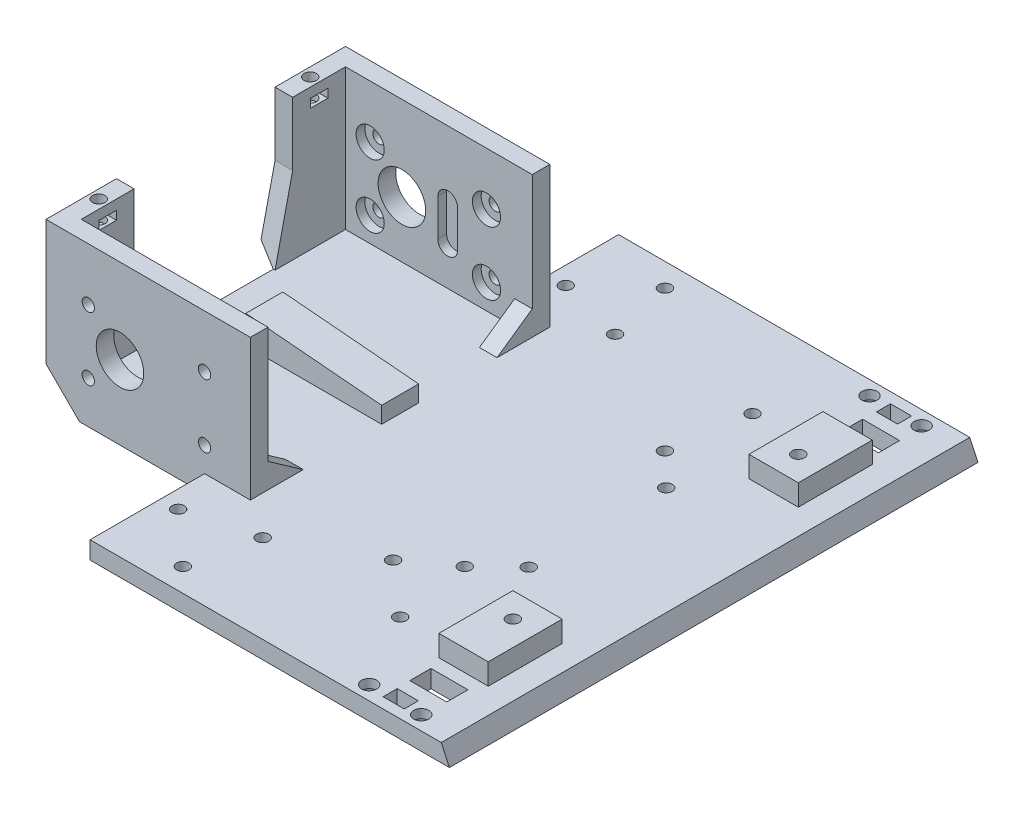
SolidWorks part; units mm, degrees
ref_plane "Front Plane" through (0, 0, 0) normal (0, 0, 1) x (1, 0, 0)
ref_plane "Top Plane" through (0, 0, 0) normal (0, 1, 0) x (1, 0, 0)
ref_plane "Right Plane" through (0, 0, 0) normal (1, 0, 0) x (0, 0, -1)
sketch "Sketch1" plane through (0, 0, 0) normal (0, 1, 0) x (1, 0, 0)
  line L0 (-25, 75) -> (-25, 42.5)
  line L1 (-25, -75) -> (77, -75)
  line L2 (-70, -42.5) -> (-70, 42.5)
  line L3 (-25, 75) -> (77, 75)
  line L4 (77, -75) -> (77, 75)
  line L7 (-25, 42.5) -> (-70, 42.5)
  line L8 (2, 0) -> (77, 0) construction
  line L9 (-25, -42.5) -> (-70, -42.5)
  line L10 (-25, -75) -> (-25, -42.5)
  point P0 (0, 0)
  dimension "D1" = 150
  dimension "D2" = 102
  dimension "D3" = 85
  dimension "D4" = 45
  dimension "D5" = 75
  dimension "D6" = 32.5
  dimension "D7" = 32.5
extrude "Boss-Extrude1" add sketch "Sketch1" along normal blind 5
sketch "Sketch3" plane through (0, 5, 0) normal (0, 1, 0) x (1, 0, 0)
  line L2 (-65, 17.5) -> (-70, 17.5)
  line L3 (-25, 42.5) -> (-70, 42.5) construction
  line L6 (-65, 17.5) -> (-65, 37.5)
  line L8 (0, 0) -> (-70, 0) construction
  line L9 (-70, 42.5) -> (-70, -42.5) construction
  line L17 (-65, 37.5) -> (-17, 37.5)
  line L18 (-12, 37.5) -> (-12, 42.5)
  line L19 (-12, 42.5) -> (-25, 42.5)
  line L20 (-25, 42.5) -> (-65, 42.5)
  line L28 (-12, 37.5) -> (-12, 27.5)
  line L29 (-12, 27.5) -> (-17, 27.5)
  line L30 (-17, 27.5) -> (-17, 37.5)
  line L40 (-70, -42.5) -> (-65, -42.5)
  line L41 (-70, 17.5) -> (-70, 42.5)
  line L42 (-70, 42.5) -> (-65, 42.5)
  line L43 (-70, -17.5) -> (-70, -42.5)
  line L44 (-17, -27.5) -> (-17, -37.5)
  line L45 (-12, -27.5) -> (-17, -27.5)
  line L46 (-12, -37.5) -> (-12, -27.5)
  line L47 (-25, -42.5) -> (-65, -42.5)
  line L48 (-12, -42.5) -> (-25, -42.5)
  line L49 (-12, -37.5) -> (-12, -42.5)
  line L50 (-65, -37.5) -> (-17, -37.5)
  line L51 (-65, -17.5) -> (-65, -37.5)
  line L52 (-65, -17.5) -> (-70, -17.5)
  line M11 (-70, -42.5) -> (-25, -42.5)
  dimension "D1" = 0
  dimension "D2" = 5
  dimension "D3" = 48
  dimension "D4" = 5
  dimension "D5" = 25
  dimension "D6" = 5
  dimension "D7" = 15
  dimension "D8" = 5
  dimension "D9" = 5
extrude "Boss-Extrude2" add sketch "Sketch3" along normal blind 32 contours M11 | L6 L17 L30 L29 L28 L18 L19 L20 L42 L41 L2 region at (-69.3684, 5, 30)
sketch "Sketch5" plane through (-70, 0, 0) normal (-1, 0, 0) x (0, 0, 1)
  line L0 (-17.5, 37) -> (-22.5, 37)
  line L1 (-17.5, 37) -> (-42.5, 37) construction
  line L2 (-22.5, 37) -> (-22.5, 27)
  line L3 (-22.5, 27) -> (-17.5, 5)
  line L4 (-17.5, 5) -> (-17.5, 37)
  line L5 (0, 0) -> (0, 35) construction
  line L6 (17.5, 5) -> (17.5, 37)
  line L7 (22.5, 27) -> (17.5, 5)
  line L8 (22.5, 37) -> (22.5, 27)
  line L9 (17.5, 37) -> (22.5, 37)
  dimension "D1" = 5
  dimension "D2" = 10
extrude "Cut-Extrude2" cut sketch "Sketch5" against normal blind 5
sketch "Sketch6" plane through (-12, 0, 0) normal (1, 0, 0) x (0, 0, -1)
  line L0 (-27.5, 37) -> (-37.5, 37)
  line L1 (-27.5, 37) -> (-42.5, 37) construction
  line L2 (-37.5, 37) -> (-37.5, 12)
  line L3 (-37.5, 12) -> (-27.5, 5)
  line L4 (-27.5, 5) -> (-27.5, 37)
  line L5 (0, 0) -> (0, 35) construction
  line L6 (37.5, 12) -> (27.5, 5)
  line L7 (37.5, 37) -> (37.5, 12)
  line L8 (27.5, 37) -> (37.5, 37)
  line L9 (27.5, 5) -> (27.5, 37)
  dimension "D1" = 10
  dimension "D2" = 25
extrude "Cut-Extrude3" cut sketch "Sketch6" against normal blind 5
sketch "Sketch7" plane through (0, 0, -42.5) normal (0, 0, -1) x (-1, 0, 0)
  line L0 (70, 37) -> (70, 0) construction
  line L1 (70, 37) -> (12, 37) construction
  line L2 (70, 37) -> (70, 0) construction
  circle A0 centre (49, 21) radius 6.75
  circle A1 centre (25, 30) radius 1.75
  circle A2 centre (25, 12) radius 1.75
  circle A3 centre (58, 30) radius 1.75
  circle A4 centre (58, 12) radius 1.75
  dimension "D1" = 21
  dimension "D2" = 13.5
  dimension "D3" = 16
  dimension "D4" = 3.5
  dimension "D5" = 7
  dimension "D6" = 12
  dimension "D7" = 3.5
  dimension "D10" = 3.5
  dimension "D12" = 3.5
  dimension "D13" = 7
  dimension "D14" = 18
  dimension "D15" = 12
  dimension "D8" = 33
  dimension "D9" = 18
  dimension "D11" = 33
extrude "Đục lỗ động cơ" cut sketch "Sketch7" against normal through all
sketch "Sketch14" plane through (0, 0, 37.5) normal (0, 0, -1) x (-1, 0, 0)
  line L0 (36, 26.25) -> (36, 15.75) construction
  line L1 (38.8, 26.25) -> (38.8, 15.75)
  line L2 (33.2, 26.25) -> (33.2, 15.75)
  line L4 (65, 37) -> (12, 37) construction
  circle A0 centre (58, 30) radius 4
  circle A1 centre (25, 30) radius 4
  circle A2 centre (25, 12) radius 4
  circle A3 centre (58, 12) radius 4
  arc A4 (38.8, 26.25) -> (33.2, 26.25) centre (36, 26.25) ccw
  arc A5 (33.2, 15.75) -> (38.8, 15.75) centre (36, 15.75) ccw
  point P14 (36, 21)
  dimension "D1" = 8
  dimension "D2" = 2.8
  dimension "D4" = 16
  dimension "D5" = 11
  dimension "D3" = 10.5
extrude "Cut-Extrude8" cut sketch "Sketch14" against normal blind 2.5
sketch "Sketch15" plane through (0, 0, -37.5) normal (0, 0, 1) x (1, 0, 0)
  line L0 (-36, 26.25) -> (-36, 15.75) construction
  line L1 (-33.2, 26.25) -> (-33.2, 15.75)
  line L2 (-38.8, 26.25) -> (-38.8, 15.75)
  line L3 (-65, 37) -> (-12, 37) construction
  circle A0 centre (-25, 30) radius 4
  circle A1 centre (-25, 12) radius 4
  circle A2 centre (-58, 12) radius 4
  circle A3 centre (-58, 30) radius 4
  arc A4 (-33.2, 26.25) -> (-38.8, 26.25) centre (-36, 26.25) ccw
  arc A5 (-38.8, 15.75) -> (-33.2, 15.75) centre (-36, 15.75) ccw
  point P14 (-36, 21)
  dimension "D1" = 8
  dimension "D2" = 2.8
  dimension "D3" = 10.5
  dimension "D4" = 16
  dimension "D5" = 11
extrude "Cut-Extrude9" cut sketch "Sketch15" against normal blind 2.5
sketch "Sketch25" plane through (0, 0, 42.5) normal (0, 0, 1) x (1, 0, 0)
  line L0 (-70, 9.5) -> (-70, 0)
  line L1 (-70, 37) -> (-70, 0) construction
  line L2 (-70, 0) -> (-60.5, 0)
  line L3 (-70, 0) -> (-25, 0) construction
  line L4 (-70, 9.5) -> (-60.5, 0)
  dimension "D1" = 9.5
extrude "Cut-Extrude15" cut sketch "Sketch25" against normal blind 89
sketch "Sketch26" plane through (0, 0, 75) normal (0, 0, 1) x (1, 0, 0)
  line L0 (77, 0) -> (49.0215, 60)
  line L1 (49.0215, 60) -> (49.0215, 0)
  line L2 (-25, 0) -> (77, 0) construction
  line L3 (49.0215, 0) -> (77, 0)
  line L4 (77, 0) -> (77, 5)
  line L5 (77, 5) -> (74.6685, 5)
  line L6 (-25, 5) -> (77, 5) construction
  line L7 (74.6685, 5) -> (77, 0)
  line M5 (77, 0) -> (77, 5)
  line M6 (77, 5) -> (-25, 5)
  dimension "D1" = 65
  dimension "D2" = 60
sketch "Sketch27" plane through (0, 37, 0) normal (0, 1, 0) x (1, 0, 0)
  line L0 (-12, 42.5) -> (-70, 42.5)
  line L1 (-70, 42.5) -> (-70, 22.5)
  line L2 (-70, 22.5) -> (-65, 22.5)
  line L3 (-65, 22.5) -> (-65, 37.5)
  line L4 (-65, 37.5) -> (-12, 37.5)
  line L5 (-12, 42.5) -> (-12, 27.5) construction
  line L6 (-12, 37.5) -> (-12, 42.5) construction
  line L7 (-12, 37.5) -> (-12, 42.5)
  line L8 (0, 0) -> (-65.5, 0) construction
  line L9 (-65.5, 17.5) -> (-65.5, -17.5) construction
  line L10 (-12, -37.5) -> (-12, -42.5)
  line L11 (-65, -37.5) -> (-12, -37.5)
  line L12 (-65, -22.5) -> (-65, -37.5)
  line L13 (-70, -22.5) -> (-65, -22.5)
  line L14 (-70, -42.5) -> (-70, -22.5)
  line L15 (-12, -42.5) -> (-70, -42.5)
extrude "Boss-Extrude3" add sketch "Sketch27" along normal blind 8
sketch "Sketch28" plane through (0, 45, 0) normal (0, 1, 0) x (1, 0, 0)
  line L0 (-70, -42.5) -> (-12, -42.5) construction
  line L1 (-65, -17.5) -> (-65, -37.5) construction
  line L2 (-65.5, 0) -> (-35.1059, 0) construction
  line L3 (-65.5, 17.5) -> (-65.5, -17.5) construction
  circle A0 centre (-67.5, -30) radius 1.75
  circle A1 centre (-67.5, 30) radius 1.75
  dimension "D2" = 2.5
  dimension "D3" = 3.5
  dimension "D1" = 12.5
extrude "Cut-Extrude16" cut sketch "Sketch28" against normal blind 7
sketch "Sketch29" plane through (-70, 0, 0) normal (-1, 0, 0) x (0, 0, 1)
  line L0 (-42.5, 45) -> (-22.5, 45) construction
  line L5 (-32.5, 42.225) -> (-27.5, 42.225)
  line L6 (-32.5, 42.225) -> (-32.5, 39.775)
  line L7 (-32.5, 39.775) -> (-27.5, 39.775)
  line L8 (-27.5, 42.225) -> (-27.5, 39.775)
  line L9 (-32.5, 42.225) -> (-27.5, 39.775) construction
  line L10 (-32.5, 39.775) -> (-27.5, 42.225) construction
  line L11 (-22.5, 45) -> (-22.5, 27) construction
  line L12 (0, 0) -> (0, 45.3888) construction
  line L13 (-42.5, 0) -> (42.5, 0) construction
  line L14 (32.5, 39.775) -> (27.5, 42.225) construction
  line L15 (32.5, 42.225) -> (27.5, 39.775) construction
  line L16 (27.5, 42.225) -> (27.5, 39.775)
  line L17 (32.5, 39.775) -> (27.5, 39.775)
  line L18 (32.5, 42.225) -> (32.5, 39.775)
  line L19 (32.5, 42.225) -> (27.5, 42.225)
  point P0 (-30.5025, 41.2857)
  point P1 (-30, 41)
  point P18 (30, 41)
  point P19 (30.5025, 41.2857)
  dimension "D1" = 5
  dimension "D2" = 2.45
  dimension "D3" = 4
  dimension "D4" = 7.5
extrude "Cut-Extrude17" cut sketch "Sketch29" against normal blind 5
extrude "Cut-Extrude18" cut sketch "Sketch26" against normal blind 151 contours L0 M5 M6 region at (76.2228, 3.3333, 75)
sketch "Sketch30" plane through (0, 0, 0) normal (0, -1, 0) x (-1, 0, 0)
  line L0 (65.5, 0) -> (-77.9904, 0) construction
  line L5 (25, -75) -> (-77, -75) construction
  line L6 (-55, 64.25) -> (-65.5, 64.25)
  line L7 (65.5, 17.5) -> (65.5, -17.5) construction
  line L8 (-55, 64.25) -> (-55, 58.25)
  line L9 (-55, 58.25) -> (-65.5, 58.25)
  line L10 (-65.5, 64.25) -> (-65.5, 58.25)
  line L11 (-55, 64.25) -> (-65.5, 58.25) construction
  line L12 (-55, 58.25) -> (-65.5, 64.25) construction
  line L13 (-77, 75) -> (25, 75) construction
  line L14 (-55, -58.25) -> (-65.5, -64.25) construction
  line L15 (-55, -64.25) -> (-65.5, -58.25) construction
  line L16 (-65.5, -64.25) -> (-65.5, -58.25)
  line L17 (-55, -58.25) -> (-65.5, -58.25)
  line L18 (-55, -64.25) -> (-55, -58.25)
  line L19 (-55, -64.25) -> (-65.5, -64.25)
  line L20 (-77, -75) -> (-77, 75) construction
  line L22 (-61.17, -72) -> (-55.17, -72)
  line L23 (-61.17, -72) -> (-61.17, -68)
  line L24 (-61.17, -68) -> (-55.17, -68)
  line L25 (-55.17, -72) -> (-55.17, -68)
  line L26 (-61.17, -72) -> (-55.17, -68) construction
  line L27 (-61.17, -68) -> (-55.17, -72) construction
  line L28 (-61.17, 68) -> (-55.17, 72) construction
  line L29 (-61.17, 72) -> (-55.17, 68) construction
  line L30 (-55.17, 72) -> (-55.17, 68)
  line L31 (-61.17, 68) -> (-55.17, 68)
  line L32 (-61.17, 72) -> (-61.17, 68)
  line L33 (-61.17, 72) -> (-55.17, 72)
  point P0 (-65.9616, 62.5602)
  point P1 (-60.25, 61.25)
  point P19 (-60.25, -61.25)
  point P20 (-65.9616, -62.5602)
  point P21 (-58.17, -70)
  point P32 (-58.17, 70)
  dimension "D1" = 6
  dimension "D2" = 10.5
  dimension "D3" = 11.5
  dimension "D4" = 16.75
  dimension "D5" = 5
  dimension "D6" = 18.83
  dimension "D7" = 4
  dimension "D8" = 6
extrude "Cut-Extrude19" cut sketch "Sketch30" against normal blind 10
sketch "Sketch31" plane through (0, 0, 0) normal (0, -1, 0) x (-1, 0, 0)
  line L0 (25, -75) -> (-77, -75) construction
  line L1 (-77, -75) -> (-77, 75) construction
  line L3 (-55.17, -72) -> (-55.17, -68) construction
  line L4 (-77, 0) -> (0, 0) construction
  circle A0 centre (-65, -71) radius 2.15
  circle A1 centre (-50.22, -71) radius 2.15
  circle A2 centre (-50.22, 71) radius 2.15
  circle A3 centre (-65, 71) radius 2.15
  dimension "D1" = 4.3
  dimension "D5" = 4.95
  dimension "D2" = 4
  dimension "D3" = 12
  dimension "D4" = 4
extrude "Cut-Extrude20" cut sketch "Sketch31" against normal blind 10
sketch "Sketch32" plane through (0, 0, 0) normal (0, -1, 0) x (-1, 0, 0)
  line L0 (-77, 0) -> (-37.6135, 0) construction
  line L1 (-77, -75) -> (-77, 75) construction
  circle A0 centre (-65, -71) radius 3.5
  circle A1 centre (-50.22, -71) radius 3.5
  circle A2 centre (-50.22, 71) radius 3.5
  circle A3 centre (-65, 71) radius 3.5
  dimension "D1" = 7
extrude "Cut-Extrude21" cut sketch "Sketch32" against normal blind 2.5
sketch "Sketch34" plane through (0, 0, 0) normal (0, -1, 0) x (-1, 0, 0)
  line L0 (60.5, 0) -> (40.5925, 0) construction
  line L1 (60.5, 42.5) -> (60.5, -42.5) construction
  line L4 (50.5462, -5.25) -> (50.5462, 5.25)
  line L6 (50.5462, 5.25) -> (56.5462, 5.25)
  line L7 (56.5462, 5.25) -> (56.5462, -5.25)
  line L8 (56.5462, -5.25) -> (50.5462, -5.25)
  point P8 (50.5462, 0)
  dimension "D1" = 10.5
  dimension "D2" = 6
extrude "Cut-Extrude23" cut sketch "Sketch34" against normal blind 5
sketch "Sketch40" plane through (0, 0, 0) normal (0, -1, 0) x (-1, 0, 0)
  line L0 (-77, -75) -> (-77, 75) construction
  line L1 (25, -75) -> (-77, -75) construction
  line L2 (-77, 0) -> (-1.5273, 0) construction
  circle A0 centre (-38, -50) radius 1.75
  circle A1 centre (-34.75, -28.4) radius 1.75
  circle A2 centre (-44, -19.5) radius 1.75
  circle A3 centre (20, -55) radius 1.75
  circle A4 centre (5.25, -68.4) radius 1.75
  circle A5 centre (1, -50) radius 1.75
  circle A6 centre (1, 50) radius 1.75
  circle A7 centre (5.25, 68.4) radius 1.75
  circle A8 centre (20, 55) radius 1.75
  circle A9 centre (-44, 19.5) radius 1.75
  circle A10 centre (-34.75, 28.4) radius 1.75
  circle A11 centre (-38, 50) radius 1.75
  dimension "D1" = 3.5
  dimension "D3" = 25
  dimension "D4" = 25
  dimension "D5" = 78
  dimension "D6" = 82.25
  dimension "D7" = 6.6
  dimension "D8" = 20
  dimension "D10" = 55.5
  dimension "D11" = 33
  dimension "D13" = 42.25
  dimension "D14" = 46.6
  dimension "D2" = 39
  dimension "D9" = 97
  dimension "D12" = 42.25
extrude "Cut-Extrude27" cut sketch "Sketch40" against normal blind 5
sketch "Sketch41" plane through (0, 5, 0) normal (0, 1, 0) x (1, 0, 0)
  line L0 (-50.5462, -5.25) -> (-50.5462, 5.25)
  line L1 (-50.5462, 5.25) -> (42.0898, 5.25)
  line L2 (42.0898, 5.25) -> (42.0898, -5.25)
  line L3 (42.0898, -5.25) -> (-50.5462, -5.25)
extrude "Boss-Extrude5" add sketch "Sketch41" along normal blind 8
sketch "Sketch42" plane through (0, 0, 5.25) normal (0, 0, 1) x (1, 0, 0)
  line L0 (42.0898, 5) -> (42.0898, 13)
  line L1 (42.0898, 13) -> (-50.5462, 13)
  line L2 (-50.5462, 13) -> (42.0898, 13) construction
  line L3 (-50.5462, 13) -> (42.0898, 5)
extrude "Cut-Extrude28" cut sketch "Sketch42" against normal blind 14
sketch "Sketch47" plane through (0, 0, 5.25) normal (0, 0, 1) x (1, 0, 0)
  line L0 (-12, 9.6712) -> (-12, 5)
  line L1 (-12, 45) -> (-12, 5) construction
  line L2 (-50.5462, 13) -> (42.0898, 5) construction
  line L3 (-12, 5) -> (42.0898, 5)
  line L4 (42.0898, 5) -> (-12, 9.6712)
extrude "Cut-Extrude34" cut sketch "Sketch47" against normal blind 13.5
sketch "Sketch48" plane through (0, 5, 0) normal (0, 1, 0) x (1, 0, 0)
  line L0 (74.6685, 75) -> (-25, 75) construction
  line L1 (53.5, 54.5) -> (67.5, 54.5)
  line L2 (53.5, 54.5) -> (53.5, 33.5)
  line L3 (53.5, 33.5) -> (67.5, 33.5)
  line L4 (67.5, 54.5) -> (67.5, 33.5)
  line L5 (53.5, 54.5) -> (67.5, 33.5) construction
  line L6 (53.5, 33.5) -> (67.5, 54.5) construction
  line L7 (77, -75) -> (77, 75) construction
  line L8 (0, 0) -> (77, 0) construction
  line L9 (53.5, -33.5) -> (67.5, -54.5) construction
  line L10 (53.5, -54.5) -> (67.5, -33.5) construction
  line L11 (67.5, -54.5) -> (67.5, -33.5)
  line L12 (53.5, -33.5) -> (67.5, -33.5)
  line L13 (53.5, -54.5) -> (53.5, -33.5)
  line L14 (53.5, -54.5) -> (67.5, -54.5)
  point P0 (60.5, 44)
  point P16 (60.5, -44)
  dimension "D1" = 20.5
  dimension "D2" = 9.5
  dimension "D3" = 14
  dimension "D4" = 21
sketch "Sketch49" plane through (0, 0, 0) normal (0, -1, 0) x (-1, 0, 0)
  line L0 (25, -75) -> (-77, -75) construction
  line L1 (-77, -75) -> (-77, 75) construction
  circle A0 centre (-23, -37) radius 1.75
  dimension "D1" = 38
  dimension "D2" = 54
  dimension "D3" = 3.5
extrude "Cut-Extrude35" cut sketch "Sketch49" against normal blind 10
extrude "Boss-Extrude6" add sketch "Sketch48" along normal blind 6
sketch "Sketch50" plane through (0, 0, 0) normal (0, -1, 0) x (-1, 0, 0)
  line L0 (-77, -75) -> (-77, 75) construction
  line L1 (25, -75) -> (-77, -75) construction
  line L2 (-77, 0) -> (0, 0) construction
  circle A0 centre (-60.5, -40.5) radius 1.75
  circle A1 centre (-60.5, 40.5) radius 1.75
  dimension "D1" = 16.5
  dimension "D2" = 3.5
  dimension "D3" = 34.5
extrude "Cut-Extrude36" cut sketch "Sketch50" against normal blind 19
sketch "Sketch51" plane through (0, 0, 0) normal (0, -1, 0) x (-1, 0, 0)
  line L0 (0, 0) -> (-77, 0) construction
  line L1 (-77, -75) -> (-77, 75) construction
  circle A0 centre (-60.5, -40.5) radius 3.1
  circle A1 centre (-44, -19.5) radius 3.1
  circle A3 centre (-34.75, -28.4) radius 3.1
  circle A4 centre (-38, -50) radius 3.1
  circle A5 centre (-23, -37) radius 3.1
  circle A6 centre (1, -50) radius 3.1
  circle A7 centre (5.25, -68.4) radius 3.1
  circle A8 centre (20, -55) radius 3.1
  circle A9 centre (20, 55) radius 3.1
  circle A10 centre (5.25, 68.4) radius 3.1
  circle A11 centre (1, 50) radius 3.1
  circle A13 centre (-38, 50) radius 3.1
  circle A14 centre (-34.75, 28.4) radius 3.1
  circle A15 centre (-44, 19.5) radius 3.1
  circle A16 centre (-60.5, 40.5) radius 3.1
  dimension "D1" = 6.2
extrude "Cut-Extrude37" cut sketch "Sketch51" against normal blind 2.5
